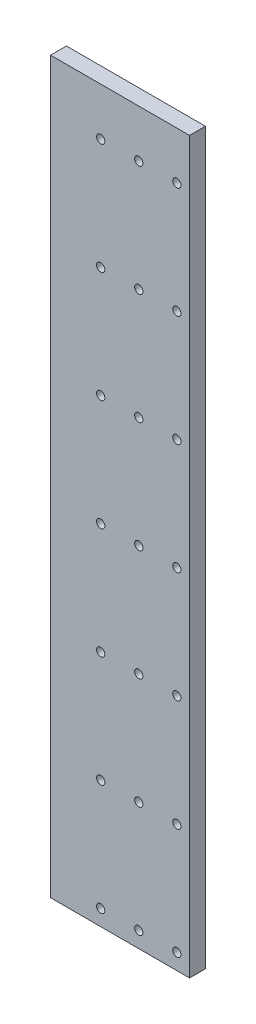
SolidWorks part; units mm, degrees
ref_plane "Plan de face" through (0, 0, 0) normal (0, 0, 1) x (1, 0, 0)
ref_plane "Plan de dessus" through (0, 0, 0) normal (0, 1, 0) x (1, 0, 0)
ref_plane "Plan de droite" through (0, 0, 0) normal (1, 0, 0) x (0, 0, -1)
sketch "Main" plane through (0, 0, 0) normal (0, 0, 1) x (1, 0, 0)
  line L1 (24.8105, 240) -> (68.6105, 240)
  line L2 (24.8105, 240) -> (24.8105, 10)
  line L3 (24.8105, 10) -> (68.6105, 10)
  line L4 (68.6105, 240) -> (68.6105, 10)
  dimension "D1" = 230
  dimension "D2" = 43.8
extrude "Main Extrusion" add sketch "Main" along normal blind 2.5
sketch "Main Fix Sketch" plane through (0, 0, 0) normal (0, 0, -1) x (-1, 0, 0)
  line L0 (-68.6105, 240) -> (-24.8105, 240) construction
  line L1 (-60.6105, 240) -> (-68.6105, 240)
  line L2 (-60.6105, 240) -> (-60.6105, 10)
  line L3 (-60.6105, 10) -> (-68.6105, 10)
  line L4 (-68.6105, 240) -> (-68.6105, 10)
  line L5 (-24.8105, 10) -> (-68.6105, 10) construction
  line L6 (-68.6105, 10) -> (-68.6105, 240) construction
  line L7 (-68.6105, 10) -> (-68.6105, 240) construction
  dimension "D1" = 0
  dimension "D2" = 8
extrude "Main Fix - Extrusion" add sketch "Main Fix Sketch" along normal blind 2.5
sketch "Main Fix Hole Sketch" plane through (0, 0, 2.5) normal (0, 0, 1) x (1, 0, 0)
  line L0 (68.6105, 10) -> (68.6105, 240) construction
  line L1 (68.6105, 240) -> (24.8105, 240) construction
  circle A0 centre (64.6105, 225) radius 1.3
  dimension "D1" = 2.6
  dimension "D2" = 4
  dimension "D3" = 15
extrude "Main Fix Hole" cut sketch "Main Fix Hole Sketch" against normal through all
pattern_linear "Main Fix Hole Horizontal Repeat" count 3 spacing 12 along (-1, 0, 0) of "Main Fix Hole"
pattern_linear "Fix Hole Vertical Repeat" count 7 spacing 35 along (0, -1, 0) of "Main Fix Hole", "Main Fix Hole Horizontal Repeat"
sketch "Vertical Rainure" plane through (0, 0, 0) normal (0, 0, -1) x (-1, 0, 0)
  line L0 (-24.8105, 240) -> (-24.8105, 10) construction
  line L1 (-24.8105, 10) -> (-29.8105, 10)
  line L2 (-24.8105, 10) -> (-24.8105, 240)
  line L3 (-24.8105, 240) -> (-29.8105, 240)
  line L4 (-29.8105, 10) -> (-29.8105, 240)
  dimension "D1" = 5
extrude "Vertical Rainure - Extrusion" add sketch "Vertical Rainure" along normal blind 2.5
sketch "Horizontal Rainure" plane through (0, 0, 0) normal (0, 0, -1) x (-1, 0, 0)
  line L0 (-68.6105, 10) -> (-60.6105, 10) construction
  line L1 (-60.6105, 16) -> (-29.8105, 16)
  line L2 (-60.6105, 16) -> (-60.6105, 10)
  line L3 (-60.6105, 10) -> (-29.8105, 10)
  line L4 (-29.8105, 16) -> (-29.8105, 10)
  dimension "D1" = 6
extrude "Horizontal Rainure - Extrusion" add sketch "Horizontal Rainure" along normal blind 2.5
pattern_linear "Répétition linéaire1" count 8 spacing 32 along (0, 1, 0) of "Horizontal Rainure - Extrusion"
pattern_linear "Répétition linéaire2" count 2 spacing 18 along (1, 0, 0) of "Vertical Rainure - Extrusion"
sketch "Slot Sketch" plane through (0, 176, 0) normal (0, 1, 0) x (1, 0, 0)
  line L0 (24.8105, 15) -> (29.8105, 15)
  line L1 (29.8105, 0) -> (42.8105, 0) construction
  line L2 (24.8105, 15) -> (24.8105, 10)
  line L3 (24.8105, 10) -> (22.6105, 10)
  line L4 (22.6105, 10) -> (22.6105, 13)
  line L5 (22.6105, 13) -> (18.8105, 10)
  line L6 (18.8105, 10) -> (18.8105, 5)
  line L7 (18.8105, 5) -> (22.6105, 2)
  line L8 (22.6105, 2) -> (22.6105, 5)
  line L9 (22.6105, 5) -> (24.8105, 5)
  line L10 (24.8105, 5) -> (24.8105, 0)
  line L11 (24.8105, 0) -> (36.3105, 0)
  line L12 (24.8105, -2.5) -> (24.8105, 2.5) construction
  line L13 (29.8105, 15) -> (36.3105, 0)
  line L15 (68.6105, -2.5) -> (24.8105, -2.5) construction
  dimension "D1" = 5
  dimension "D2" = 8
  dimension "D3" = 2.2
  dimension "D4" = 3.8
  dimension "D5" = 5
  dimension "D6" = 7.5
  dimension "D7" = 17.5
extrude "Slot Sketch Extrusion" add sketch "Slot Sketch" along normal blind 20
ref_plane "Plan1" through (32.8105, 0, 0) normal (-1, 0, 0) x (0, 0, 1)
ref_axis "Axe Fox Clip Fix Sketch" through (32.8105, 252, -15) along (0, -1, 0)
sketch "Clip Fix Sketch" plane through (0, 0, -15) normal (0, 0, -1) x (-1, 0, 0)
  line L0 (-24.8105, 196) -> (-24.8105, 176) construction
  line L1 (-26.8105, 178) -> (-28.8105, 178)
  line L2 (-26.8105, 178) -> (-26.8105, 182)
  line L3 (-26.8105, 182) -> (-28.8105, 182)
  line L4 (-28.8105, 178) -> (-28.8105, 182)
  line L5 (-29.8105, 176) -> (-24.8105, 176) construction
  line L7 (-28.8105, 190) -> (-26.8105, 190)
  line L8 (-28.8105, 190) -> (-28.8105, 194)
  line L9 (-28.8105, 194) -> (-26.8105, 194)
  line L10 (-26.8105, 190) -> (-26.8105, 194)
  line L11 (-29.8105, 196) -> (-24.8105, 196) construction
  dimension "D1" = 4
  dimension "D2" = 2
  dimension "D3" = 2
  dimension "D4" = 2
  dimension "D5" = 2
revolve "Clip Fix Extrusion" cut sketch "Clip Fix Sketch" angle 360 about axis through (32.8105, 252, -15) along (0, -1, 0)
sketch "Slot Hole Sketch" plane through (18.8105, 0, 0) normal (-1, 0, 0) x (0, 0, 1)
  line L0 (-10, 176) -> (-5, 176) construction
  line L1 (-5, 196) -> (-5, 176) construction
  circle A0 centre (-7.5, 186) radius 1.3
  point P5 (-7.5, 176)
  point P8 (-5, 186)
  dimension "D1" = 2.6
extrude "Slot Hole Extrusion" cut sketch "Slot Hole Sketch" against normal through all
sketch "Slot Hole Head" plane through (32.8105, 0, 0) normal (-1, 0, 0) x (0, 0, 1)
  circle A0 centre (-7.5, 186) radius 3
  circle A1 centre (-7.5, 186) radius 1.3 construction
  dimension "D1" = 6
extrude "Slot Hole Head Extrusion" cut sketch "Slot Hole Head" along normal mid plane 6
pattern_linear "Répétition linéaire3" count 3 spacing 80 along (0, -1, 0) of "Slot Sketch Extrusion", "Clip Fix Extrusion", "Slot Hole Extrusion", "Slot Hole Head Extrusion"
